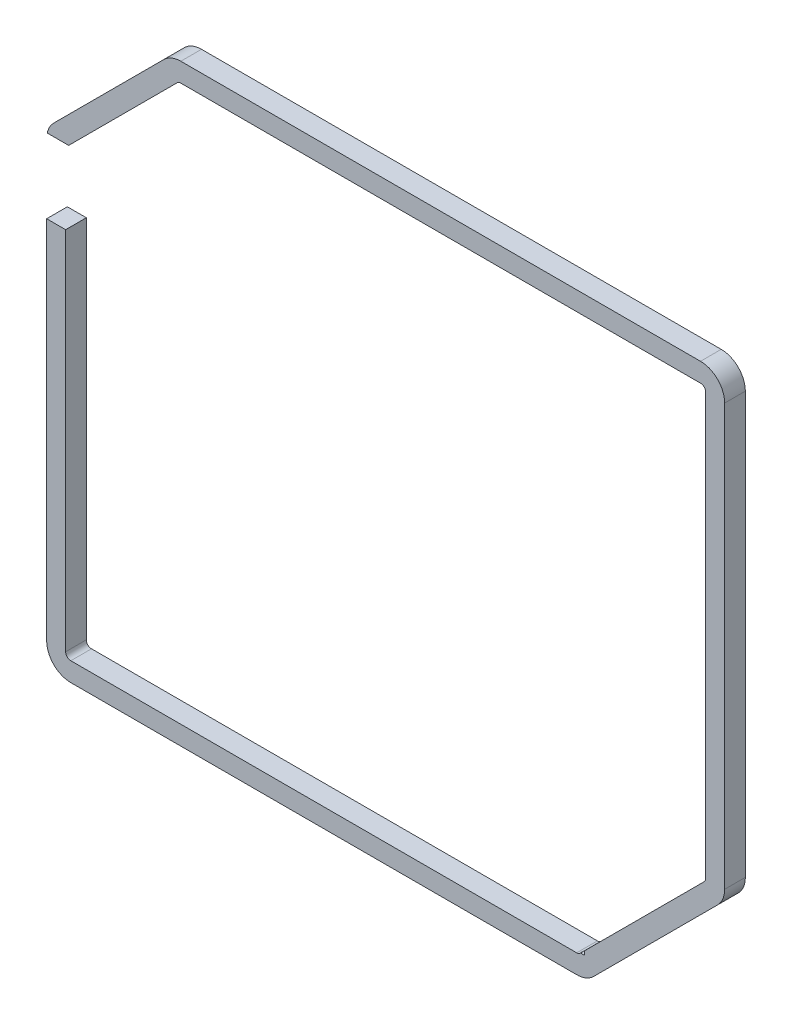
SolidWorks part; units mm, degrees
material "Acrylic (Medium-high impact)"
ref_plane "Front Plane" through (0, 0, 0) normal (0, 0, 1) x (1, 0, 0)
ref_plane "Top Plane" through (0, 0, 0) normal (0, 1, 0) x (1, 0, 0)
ref_plane "Right Plane" through (0, 0, 0) normal (1, 0, 0) x (0, 0, -1)
sketch "Sketch1" plane through (0, 0, 0) normal (0, 0, 1) x (1, 0, 0)
  line L0 (0, 66) -> (-18, 48)
  line L1 (0, 0) -> (80.3, 0)
  line L2 (0, 0) -> (0, 66)
  line L3 (0, 66) -> (80.3, 66)
  line L4 (80.3, 0) -> (80.3, 66)
  line L5 (-18, 48) -> (-18, -20)
  line L6 (-18, -20) -> (60.3, -20)
  line L7 (60.3, -20) -> (80.3, 0)
  dimension "D1" = 80.3
  dimension "D2" = 66
  dimension "D3" = 20
  dimension "D4" = 18
  dimension "D5" = 45
  dimension "D6" = 45
extrude "Boss-Extrude1" add sketch "Sketch1" along normal blind 3 contours L6 L7 L1 L2 L0 L5 | L1 L4 L3 L2 region at (-1.3061, 33, 0) region at (40.15, 33, 0)
fillet "Fillet1" radius 3.5 6 edges at (80.3, 0, 1.5) (60.3, -20, 1.5) (-18, -20, 1.5) (-18, 48, 1.5) (80.3, 66, 1.5) (0, 66, 1.5)
sketch "Sketch2" plane through (0, 0, 3) normal (0, 0, 1) x (1, 0, 0)
  line L1 (3, 10.5) -> (75.4, 10.5)
  line L2 (3, 10.5) -> (3, 55.5)
  line L3 (3, 55.5) -> (75.4, 55.5)
  line L4 (75.4, 10.5) -> (75.4, 55.5)
  line L6 (80.3, 1.4497) -> (80.3, 62.5) construction
  line L7 (1.4497, 66) -> (76.8, 66) construction
  dimension "D1" = 4.9
  dimension "D2" = 3
  dimension "D3" = 10.5
  dimension "D4" = 45
extrude "Cut-Extrude1" cut sketch "Sketch2" against normal through all contours L1 L4 L3 L2 region at (39.2, 33, 3)
sketch "Sketch3" plane through (0, 0, 3) normal (0, 0, 1) x (1, 0, 0)
  line L1 (27, -17) -> (60, -17)
  line L2 (27, -17) -> (27, 1)
  line L3 (27, 1) -> (60, 1)
  line L4 (60, -17) -> (60, 1)
  line L5 (-15, -17) -> (24, -17)
  line L6 (-15, -17) -> (-15, 1.5)
  line L7 (-15, 1.5) -> (24, 1.5)
  line L8 (24, -17) -> (24, 1.5)
  line L9 (0, 4.5) -> (-15, 4.5)
  line L10 (0, 4.5) -> (0, 34.5)
  line L11 (0, 34.5) -> (-15, 34.5)
  line L12 (-15, 4.5) -> (-15, 34.5)
  line L13 (-18, 47.3) -> (-3, 47.3)
  line L14 (-18, 47.3) -> (-18, 36.5)
  line L15 (-18, 36.5) -> (-3, 36.5)
  line L16 (-3, 47.3) -> (-3, 36.5)
  line L17 (-14.5, -20) -> (58.8503, -20) construction
  line L18 (-18, 46.5503) -> (-18, -16.5) construction
  line L21 (67.2426, -8.8147) -> (71.4853, -4.5721)
  line L22 (71.4853, -4.5721) -> (67.2426, -0.3294)
  line L23 (67.2426, -0.3294) -> (63, -4.5721)
  line L24 (63, -4.5721) -> (67.2426, -8.8147)
  line L25 (61.3251, -18.9749) -> (79.2749, -1.0251) construction
  arc M12 (-16.9749, 49.0251) -> (-18, 46.5503) centre (-14.5, 46.5503) ccw
  line M13 (-18, 46.5503) -> (-18, -16.5)
  dimension "D1" = 18
  dimension "D2" = 18.5
  dimension "D3" = 39
  dimension "D4" = 33
  dimension "D5" = 15
  dimension "D6" = 30
  dimension "D7" = 10.8
  dimension "D8" = 15
  dimension "D9" = 3
  dimension "D10" = 3
  dimension "D11" = 3
  dimension "D12" = 3
  dimension "D13" = 3
  dimension "D14" = 3
  dimension "D15" = 2
  dimension "D16" = 6
  dimension "D17" = 6
  dimension "D18" = 6
  dimension "D19" = 3
  dimension "D20" = 3
extrude "Cut-Extrude2" cut sketch "Sketch3" against normal through all contours L16 L13 L15 M12 M13 | L12 L9 L10 L11 | L1 L4 L3 L2 | L5 L8 L7 L6 | L23 L24 L21 L22 region at (43.5, -8, 3) region at (4.5, -7.75, 3) region at (-7.5, 19.5, 3) region at (-10.4991, 41.8993, 3) region at (67.2426, -4.5721, 3)
sketch "Sketch4" plane through (0, 0, 3) normal (0, 0, 1) x (1, 0, 0)
  line L0 (-1.0251, 64.9749) -> (-16.9749, 49.0251) construction
  line L1 (1.4497, 66) -> (76.8, 66) construction
  line L2 (80.3, 1.4497) -> (80.3, 62.5) construction
  line L3 (61.3251, -18.9749) -> (79.2749, -1.0251) construction
  line L4 (-14.5, -20) -> (58.8503, -20) construction
  line L5 (-18, 36.5) -> (-18, -16.5) construction
  line L6 (-1.0251, 64.9749) -> (-16.9749, 49.0251)
  line L7 (1.4497, 66) -> (76.8, 66)
  line L8 (80.3, 1.4497) -> (80.3, 62.5)
  line L9 (61.3251, -18.9749) -> (79.2749, -1.0251)
  line L10 (-14.5, -20) -> (58.8503, -20)
  line L11 (-18, 36.5) -> (-18, -16.5)
  line L12 (-18, 36.5) -> (-17.9188, 47.3)
  line L13 (0.9194, 63.0303) -> (-15.0303, 47.0806)
  line L14 (-15.25, 36.4897) -> (-15.1718, 46.8837)
  line L15 (-15.25, 36.4897) -> (-15.25, -16.5)
  line L16 (-14.5, -17.25) -> (58.8503, -17.25)
  line L17 (59.3806, -17.0303) -> (77.3303, 0.9194)
  line L18 (77.55, 1.4497) -> (77.55, 62.5)
  line L19 (1.4497, 63.25) -> (76.8, 63.25)
  arc A0 (1.4497, 66) -> (-1.0251, 64.9749) centre (1.4497, 62.5) ccw construction
  arc A1 (-16.9749, 49.0251) -> (-17.9188, 47.3) centre (-14.5, 46.5503) ccw construction
  arc A2 (80.3, 62.5) -> (76.8, 66) centre (76.8, 62.5) ccw construction
  arc A3 (79.2749, -1.0251) -> (80.3, 1.4497) centre (76.8, 1.4497) ccw construction
  arc A4 (58.8503, -20) -> (61.3251, -18.9749) centre (58.8503, -16.5) ccw construction
  arc A5 (-18, -16.5) -> (-14.5, -20) centre (-14.5, -16.5) ccw construction
  arc A6 (1.4497, 66) -> (-1.0251, 64.9749) centre (1.4497, 62.5) ccw
  arc A7 (-16.9749, 49.0251) -> (-17.9188, 47.3) centre (-14.5, 46.5503) ccw
  arc A8 (80.3, 62.5) -> (76.8, 66) centre (76.8, 62.5) ccw
  arc A9 (79.2749, -1.0251) -> (80.3, 1.4497) centre (76.8, 1.4497) ccw
  arc A10 (58.8503, -20) -> (61.3251, -18.9749) centre (58.8503, -16.5) ccw
  arc A11 (-18, -16.5) -> (-14.5, -20) centre (-14.5, -16.5) ccw
  arc A12 (-15.0303, 47.0806) -> (-15.1718, 46.8837) centre (-14.5, 46.5503) ccw
  arc A13 (-15.25, -16.5) -> (-14.5, -17.25) centre (-14.5, -16.5) ccw
  arc A14 (58.8503, -17.25) -> (59.3806, -17.0303) centre (58.8503, -16.5) ccw
  arc A15 (77.3303, 0.9194) -> (77.55, 1.4497) centre (76.8, 1.4497) ccw
  arc A16 (77.55, 62.5) -> (76.8, 63.25) centre (76.8, 62.5) ccw
  arc A17 (1.4497, 63.25) -> (0.9194, 63.0303) centre (1.4497, 62.5) ccw
  line M1 (63, -4.5721) -> (67.2426, -0.3294)
  line M2 (67.2426, -0.3294) -> (71.4853, -4.5721)
  line M3 (71.4853, -4.5721) -> (67.2426, -8.8147)
  line M4 (67.2426, -8.8147) -> (63, -4.5721)
  line M5 (24, -17) -> (-15, -17)
  line M6 (-15, -17) -> (-15, 1.5)
  line M7 (-15, 1.5) -> (24, 1.5)
  line M8 (24, 1.5) -> (24, -17)
  line M9 (60, -17) -> (27, -17)
  line M10 (27, -17) -> (27, 1)
  line M11 (27, 1) -> (60, 1)
  line M12 (60, 1) -> (60, -17)
  line M13 (75.4, 10.5) -> (3, 10.5)
  line M14 (3, 10.5) -> (3, 55.5)
  line M15 (3, 55.5) -> (75.4, 55.5)
  line M16 (75.4, 55.5) -> (75.4, 10.5)
  line M17 (-3, 36.5) -> (-18, 36.5)
  line M30 (-17.9188, 47.3) -> (-3, 47.3)
  line M31 (-3, 47.3) -> (-3, 36.5)
  line M32 (0, 4.5) -> (-15, 4.5)
  line M33 (-15, 4.5) -> (-15, 34.5)
  line M34 (-15, 34.5) -> (0, 34.5)
  line M35 (0, 34.5) -> (0, 4.5)
  dimension "D1" = 2.75
extrude "Cut-Extrude3" cut sketch "Sketch4" against normal through all contours L19 A17 L13 L14 L15 A13 L16 A14 L17 A15 L18 A16 M30 M31 M17 M9 M10 M11 M12 M4 M1 M2 M3 M35 M32 M33 M34 M16 M13 M14 M15 M8 M5 M6 M7 region at (-6.0771, 54.2965, 3)
